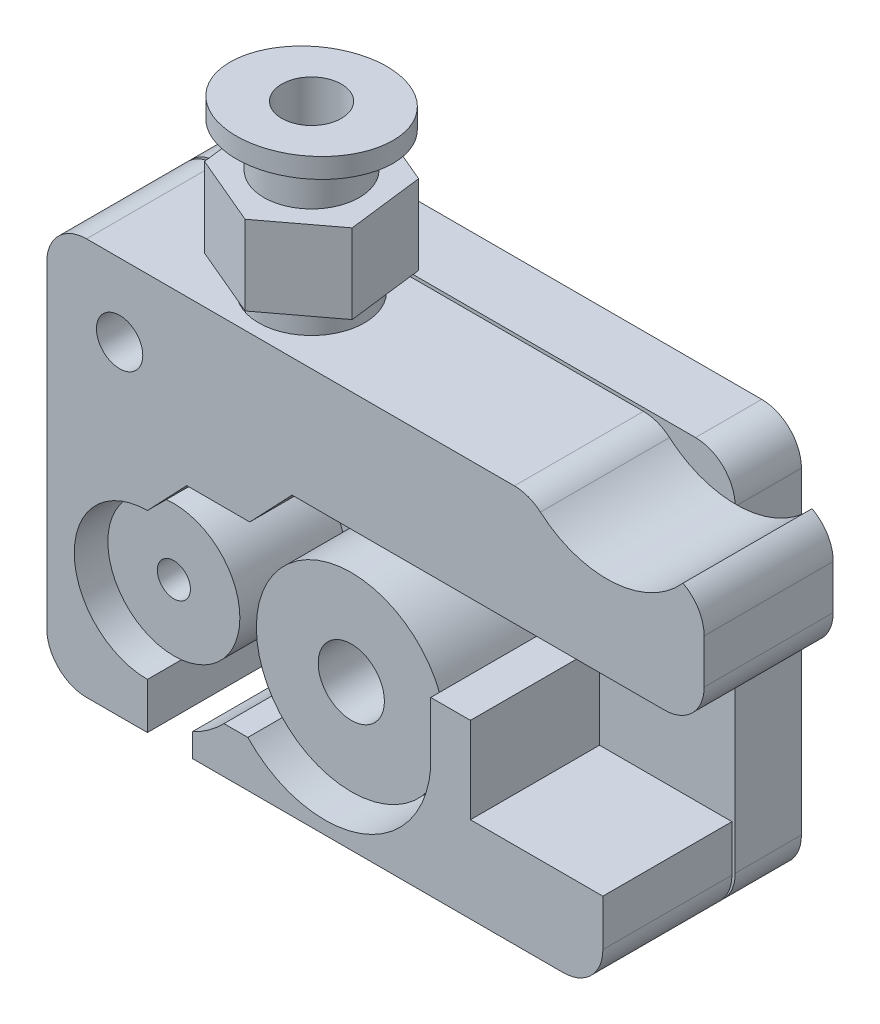
SolidWorks part; units mm, degrees
ref_plane "Front Plane" through (0, 0, 0) normal (0, 0, 1) x (1, 0, 0)
ref_plane "Top Plane" through (0, 0, 0) normal (0, 1, 0) x (1, 0, 0)
ref_plane "Right Plane" through (0, 0, 0) normal (1, 0, 0) x (0, 0, -1)
sketch "Sketch1" plane through (0, 0, 0) normal (0, 0, 1) x (1, 0, 0)
  line L1 (-21, -15) -> (21, -15)
  line L2 (-21, -15) -> (-21, 15)
  line L3 (-21, 15) -> (21, 15)
  line L4 (21, -15) -> (21, 15)
  line L5 (-21, -15) -> (21, 15) construction
  line L6 (-21, 15) -> (21, -15) construction
  point P0 (0, 0)
  dimension "D1" = 42
  dimension "D2" = 30
extrude "Boss-Extrude1" add sketch "Sketch1" along normal blind 5
sketch "Sketch2" plane through (0, 0, 5) normal (0, 0, 1) x (1, 0, 0)
  line L0 (8, -6.57) -> (8, -2)
  line L1 (8, -2) -> (11, -2)
  line L2 (-21, 15) -> (15.5487, 15)
  line L3 (11, -2) -> (11, -8.5)
  line L4 (-21, 15) -> (-21, -15)
  line L5 (-21, -15) -> (-13.4022, -15)
  line L6 (21, -8.5) -> (21, -15)
  line L7 (11, -8.5) -> (21, -8.5)
  line L8 (21, -8.5) -> (21, -15)
  line L9 (-10, -15) -> (-10, -13.2373)
  line L10 (-7.6188, -11.5232) -> (-5.8154, -11.5232)
  line L11 (-13.4022, -15) -> (-13.4022, -11.5232)
  line L12 (-13.4022, -0.4768) -> (-10.4334, 2.6417)
  line L13 (-10.4334, 2.6417) -> (-5.6699, 2.6417)
  line L14 (-5.6699, 2.6417) -> (-2.4728, 6)
  line L15 (-2.4728, 6) -> (28.6504, 6)
  line L16 (28.6504, 6) -> (28.6504, 15)
  line L17 (28.6504, 15) -> (27.0513, 15)
  line L18 (-10, -15) -> (21, -15)
  arc A0 (-13.4022, -0.4768) -> (-13.4022, -11.5232) centre (-13.4022, -6) ccw
  arc A1 (8, -6.57) -> (-5.8154, -11.5232) centre (0, -6) cw
  arc A2 (-10, -13.2373) -> (-7.6188, -11.5232) centre (-13.4022, -6) ccw
  arc A3 (15.5487, 15) -> (27.0513, 15) centre (21.3, 20.0537) ccw
  line M1 (21, 15) -> (-21, 15)
  line M3 (-21, 15) -> (-21, -15)
  line M5 (-21, -15) -> (21, -15)
  line M7 (21, -15) -> (21, 15)
  dimension "D1" = 42
  dimension "D2" = 6.5
  dimension "D3" = 3
  dimension "D4" = 10
  dimension "D5" = 7.5978
  dimension "D6" = 21
  dimension "D7" = 30
  dimension "D8" = 21
  dimension "D9" = 9
  dimension "D10" = 13
  dimension "D11" = 21
  dimension "D12" = 31
extrude "Boss-Extrude2" add sketch "Sketch2" along normal blind 9.75 from offset 0.25 separate body contours A3 L11 A0 L12 L13 L14 L15 M1 M3 M5 M7 | A2 L9 L7 L3 L1 L0 A1 L10 M5 M7 | A3 L15 L16 L17 M7
fillet "Fillet1" radius 3 4 edges at (-21, -15, 2.5) (21, -15, 2.5) (21, 15, 2.5) (-21, 15, 2.5)
sketch "Sketch6" plane through (0, 15, 0) normal (0, 1, 0) x (1, 0, 0)
  line L0 (-21, -15) -> (-21, -5.25) construction
  line L1 (15.5487, -15) -> (-21, -15) construction
  circle A0 centre (-6, -10) radius 4
  circle A1 centre (-6, -10) radius 2.25
  dimension "D1" = 8
  dimension "D2" = 4.5
  dimension "D3" = 15
  dimension "D4" = 5
extrude "Boss-Extrude3" add sketch "Sketch6" along normal blind 2 contours A1 | A0
fillet "Fillet2" radius 3 1 edges at (-21, 15, 10.125)
fillet "Fillet3" radius 3 1 edges at (21, -15, 10.125)
fillet "Fillet4" radius 3 4 edges at (-21, -15, 10.125) (28.6504, 15, 10.125) (28.6504, 6, 10.125) (15.5487, 15, 10.125)
sketch "Sketch13" plane through (0, 17, 0) normal (0, 1, 0) x (1, 0, 0)
  line L1 (-0.6833, -12.2509) -> (-1.3923, -6.5211)
  line L2 (-1.3923, -6.5211) -> (-6.709, -4.2702)
  line L3 (-6.709, -4.2702) -> (-11.3167, -7.7491)
  line L4 (-11.3167, -7.7491) -> (-10.6077, -13.4789)
  line L5 (-10.6077, -13.4789) -> (-5.291, -15.7298)
  line L6 (-5.291, -15.7298) -> (-0.6833, -12.2509)
  circle A0 centre (-6, -10) radius 5 construction
  dimension "D1" = 10
extrude "Boss-Extrude5" add sketch "Sketch13" along normal blind 6
sketch "Sketch14" plane through (0, 23, 0) normal (0, 1, 0) x (1, 0, 0)
  circle A0 centre (-6, -10) radius 3.605
extrude "Boss-Extrude6" add sketch "Sketch14" along normal blind 2
sketch "Sketch15" plane through (0, 25, 0) normal (0, 1, 0) x (1, 0, 0)
  circle A0 centre (-6, -10) radius 2.5927
extrude "Boss-Extrude7" add sketch "Sketch15" along normal blind 1
sketch "Sketch16" plane through (0, 26, 0) normal (0, 1, 0) x (1, 0, 0)
  ellipse E0 centre (-6, -10) end of major axis (-11.2972, -12.2365) minor radius 5
extrude "Boss-Extrude8" add sketch "Sketch16" along normal blind 1.5
sketch "Sketch20" plane through (0, 15, 0) normal (0, 1, 0) x (1, 0, 0)
  circle A0 centre (-6, -10) radius 1.25
sketch "Sketch9" plane through (0, 0, 5) normal (0, 0, 1) x (1, 0, 0)
  line L0 (21, -12) -> (21, 12) construction
  line L4 (18, 15) -> (-18, 15) construction
  circle A0 centre (-13.4022, -6) radius 4.9851
  circle A1 centre (0, -6) radius 7.1716
  dimension "D1" = 21
  dimension "D2" = 21
sketch "Sketch10" plane through (0, 0, 0) normal (0, 0, -1) x (-1, 0, 0)
  line L0 (-18, 15) -> (18, 15) construction
  line L1 (-21, -12) -> (-21, 12) construction
  circle A0 centre (0, -6) radius 11
  dimension "D1" = 21
  dimension "D2" = 21
sketch "Sketch8" plane through (0, 0, 0) normal (0, 0, 1) x (1, 0, 0)
  line L1 (-21, 12) -> (-21, -12) construction
  line L2 (18, 15) -> (-18, 15) construction
  circle A0 centre (15.5, 9.5) radius 1.75
  circle A1 centre (-15.5, 9.5) radius 1.75
  dimension "D4" = 3.5
  dimension "D1" = 31
  dimension "D2" = 5.5
  dimension "D3" = 5.5
extrude "Cut-Extrude10" cut sketch "Sketch8" along normal blind 5
sketch "Sketch5" plane through (0, 0, 5) normal (0, 0, 1) x (1, 0, 0)
  line L0 (14.322, 15) -> (-18, 15) construction
  line L1 (21, -12) -> (21, 12) construction
  circle A0 centre (0, -6) radius 8.15
  dimension "D1" = 21
  dimension "D2" = 21
extrude "Cut-Extrude2" cut sketch "Sketch5" against normal blind 10 contours A0
extrude "Cut-Extrude11" cut sketch "Sketch10" against normal blind 2
sketch "Sketch19" plane through (0, 27.5, 0) normal (0, 1, 0) x (1, 0, 0)
  circle A0 centre (-6, -10) radius 2.25
extrude "Cut-Extrude14" cut sketch "Sketch19" against normal blind 11
sketch "Sketch17" plane through (0, 0, 15) normal (0, 0, 1) x (1, 0, 0)
  circle A0 centre (-15.5, 9.5) radius 1.75
extrude "Cut-Extrude12" cut sketch "Sketch17" against normal through all
extrude "Boss-Extrude9" add sketch "Sketch9" along normal blind 8
sketch "Sketch21" plane through (0, 0, 13) normal (0, 0, 1) x (1, 0, 0)
  circle A0 centre (0, -6) radius 2.5
  circle A1 centre (-13.4022, -6) radius 1.25
extrude "Cut-Extrude17" cut sketch "Sketch21" against normal blind 8
extrude "Cut-Extrude16" cut sketch "Sketch20" against normal blind 30
mirror "Mirror2" [suppressed]
delete or keep bodies "Body-Delete/Keep 1" [suppressed] type delete bodies bodies 144 149 152 148 153
